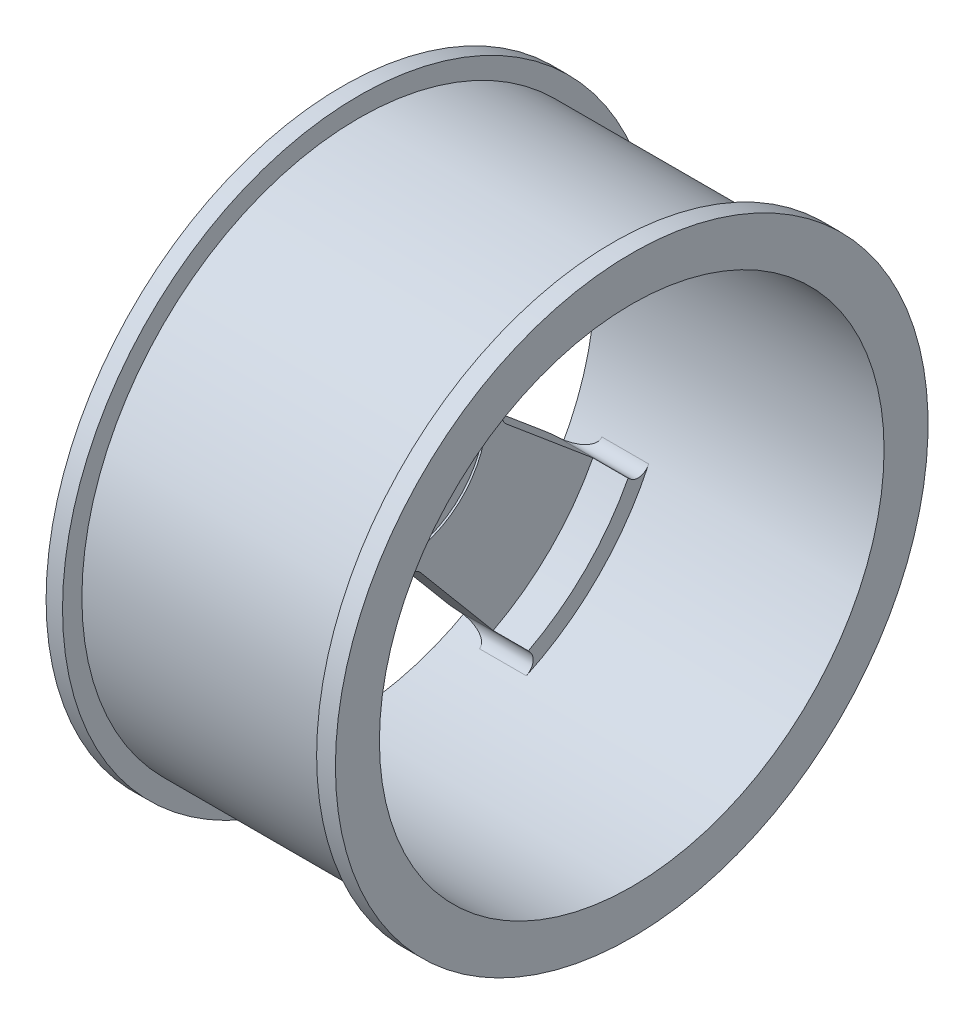
SolidWorks part; units mm, degrees
material "6061-T6 (SS)"
ref_plane "Front Plane" through (0, 0, 0) normal (0, 0, 1) x (1, 0, 0)
ref_plane "Top Plane" through (0, 0, 0) normal (0, 1, 0) x (1, 0, 0)
ref_plane "Right Plane" through (0, 0, 0) normal (1, 0, 0) x (0, 0, -1)
sketch "Sketch1" plane through (0, 0, 0) normal (0, 0, 1) x (1, 0, 0)
  line L0 (0, 0) -> (59.4628, 0) construction
  line L1 (0, 202) -> (0, 172)
  line L2 (0, 172) -> (28.8, 172)
  line L3 (28.8, 172) -> (28.8, 160)
  line L4 (28.8, 160) -> (52.8, 160)
  line L5 (52.8, 160) -> (52.8, 172)
  line L6 (52.8, 172) -> (197.2, 172)
  line L7 (197.2, 172) -> (197.2, 202)
  line L8 (197.2, 202) -> (184.4, 202)
  line L9 (184.4, 202) -> (184.4, 188.8)
  line L10 (184.4, 188.8) -> (11.2, 188.8)
  line L11 (11.2, 188.8) -> (11.2, 202)
  line L12 (11.2, 202) -> (0, 202)
  dimension "D1" = 202
  dimension "D2" = 188.8
  dimension "D3" = 172
  dimension "D4" = 160
  dimension "D5" = 28.8
  dimension "D6" = 24
  dimension "D7" = 11.2
  dimension "D8" = 12.8
  dimension "D9" = 197.2
revolve "Revolve1" add sketch "Sketch1" angle 360 about L0
sketch "Sketch2" plane through (0, 0, 0) normal (0, 0, 1) x (1, 0, 0)
  line L0 (-3.1546, 0) -> (32.0631, 0) construction
  line L1 (12, 0) -> (12, 74)
  line L2 (12, 74) -> (70.8897, 40)
  line L3 (70.8897, 40) -> (217.6, 40)
  line L4 (217.6, 40) -> (217.6, 0)
  line L5 (217.6, 0) -> (12, 0)
  line L6 (0, 172) -> (0, -172) construction
  dimension "D1" = 74
  dimension "D2" = 12
  dimension "D3" = 40
  dimension "D4" = 60
  dimension "D5" = 205.6
revolve "Revolve2" add sketch "Sketch2" angle 360 about L0
sketch "Sketch4" plane through (0, 0, 0) normal (0, 0, 1) x (1, 0, 0)
  line L0 (28.8, 172) -> (20.7846, 172)
  line L1 (28.8, 172) -> (28.8, -172) construction
  line L2 (20.7846, 172) -> (0, 160)
  line L3 (0, 172) -> (0, -172) construction
  line L4 (0, 160) -> (0, 0)
  line L5 (0, 0) -> (12, 0)
  line L6 (12, 74) -> (12, -74) construction
  line L7 (12, 0) -> (12, 10.8005)
  line L8 (12, 10.8005) -> (28.8, 20.5)
  line L9 (28.8, 160) -> (28.8, -160) construction
  line L10 (28.8, 20.5) -> (28.8, 172)
  dimension "D3" = 172
  dimension "D1" = 12
  dimension "D2" = 160
  dimension "D4" = 20.5
  dimension "D5" = 120
  dimension "D6" = 151.5
  dimension "D7" = 8.0154
revolve "Revolve3" add sketch "Sketch4" angle 360 about L5
fillet "Fillet1" radius 8 1 edges at (0, 0, 160)
sketch "Sketch5" plane through (0, 0, 0) normal (-1, 0, 0) x (0, 0, 1)
  line L0 (0, 0) -> (0, 202) construction
  line L1 (22, 80) -> (-22, 80)
  line L2 (-22, 80) -> (-81.8212, 151.2921)
  line L3 (22, 80) -> (81.8212, 151.2921)
  line L4 (80, 22) -> (151.2921, 81.8212)
  line L5 (80, -22) -> (80, 22)
  line L6 (80, -22) -> (151.2921, -81.8212)
  line L7 (22, -80) -> (81.8212, -151.2921)
  line L8 (-22, -80) -> (22, -80)
  line L9 (-22, -80) -> (-81.8212, -151.2921)
  line L10 (-80, -22) -> (-151.2921, -81.8212)
  line L11 (-80, 22) -> (-80, -22)
  line L12 (-80, 22) -> (-151.2921, 81.8212)
  circle A0 centre (0, 0) radius 202 construction
  circle A3 centre (0, 0) radius 172 construction
  arc A4 (81.8212, 151.2921) -> (-81.8212, 151.2921) centre (0, 0) ccw
  arc A5 (151.2921, -81.8212) -> (151.2921, 81.8212) centre (0, 0) ccw
  arc A6 (-81.8212, -151.2921) -> (81.8212, -151.2921) centre (0, 0) ccw
  arc A7 (-151.2921, 81.8212) -> (-151.2921, -81.8212) centre (0, 0) ccw
  point P13 (0, 80)
  point P28 (0, 0)
  dimension "D1" = 44
  dimension "D2" = 80
  dimension "D3" = 130
  dimension "D4" = 130
  dimension "D5" = 4
extrude "Cut-Extrude3" cut sketch "Sketch5" against normal through all
fillet "Fillet4" radius 8 2 edges at (14.4, 80, 22) (14.4, 80, -22)
fillet "Fillet6" radius 8 2 edges at (14.4, -22, 80) (14.4, 22, 80)
fillet "Fillet7" radius 8 8 edges at (36.7923, -151.2921, -81.8212) (36.7923, -81.8212, -151.2921) (36.7923, -151.2921, 81.8212) (36.7923, 81.8212, -151.2921) (14.4, -80, -22) (14.4, -80, 22) (14.4, -22, -80) (14.4, 22, -80)
sketch "Sketch7" plane through (0, 0, 0) normal (0, 0, 1) x (1, 0, 0)
  line L0 (0, 0) -> (17.1078, 0) construction
  line L1 (0, 0) -> (0, 68)
  line L2 (0, 24.3979) -> (0, 70.8916) construction
  line L3 (0, 68) -> (24.8, 53.6817)
  line L4 (24.8, 53.6817) -> (24.8, 0)
  line L5 (24.8, 0) -> (0, 0)
  dimension "D1" = 24.8
  dimension "D2" = 68
  dimension "D3" = 60
revolve "Cut-Revolve3" cut sketch "Sketch7" angle 360 about L0
sketch "Sketch8" plane through (24.8, 0, 0) normal (-1, 0, 0) x (0, 0, 1)
  circle A0 centre (0, 0) radius 36
  circle A1 centre (0, 44.45) radius 3.937
  circle A2 centre (44.45, 0) radius 3.937
  circle A3 centre (0, 0) radius 36
  circle A4 centre (0, -44.45) radius 3.937
  circle A5 centre (0, 0) radius 36
  circle A6 centre (-44.45, 0) radius 3.937
  circle A7 centre (0, 0) radius 36
  point P17 (0, 0)
  dimension "D1" = 72
  dimension "D2" = 7.874
  dimension "D3" = 44.45
  dimension "D4" = 4
extrude "Boss-Extrude1" add sketch "Sketch8" along normal blind 1 contours A0 region at (24.8, 0, 0)
extrude "Cut-Extrude6" cut sketch "Sketch8<6>" against normal through all contours A1 | A2 | A4 | A6 region at (24.8, 44.45, 0) region at (24.8, 0, 44.45) region at (24.8, -44.45, 0)
sketch "Sketch8<6>" plane through (24.8, 0, 0) normal (-1, 0, 0) x (0, 0, 1) same geometry as "Sketch8"
sketch "Sketch9" plane through (217.6, 0, 0) normal (1, 0, 0) x (0, 0, -1)
  circle A0 centre (0, 0) radius 57.15
  dimension "D1" = 114.3
extrude "Cut-Extrude7" cut sketch "Sketch9" against normal blind 177.8
equation "\"scale\"= 8"
equation "\"D7@Sketch1\"=1.40mm * \"scale\""
equation "\"D9@Sketch1\"=24.65mm * \"scale\""
equation "\"D8@Sketch1\"=1.60mm * \"scale\""
equation "\"D1@Sketch1\"=25.25mm * \"scale\""
equation "\"D2@Sketch1\"=23.60mm * \"scale\""
equation "\"D3@Sketch1\"=21.50mm * \"scale\""
equation "\"D4@Sketch1\"=20.00mm * \"scale\""
equation "\"D5@Sketch1\"=3.60mm * \"scale\""
equation "\"D6@Sketch1\"=3.00mm * \"scale\""
equation "\"D1@Sketch2\"=9.25mm * \"scale\""
equation "\"D3@Sketch2\"=5.00mm * \"scale\""
equation "\"D2@Sketch2\"=1.50mm * \"scale\""
equation "\"D5@Sketch2\"=25.70mm * \"scale\""
equation "\"D1@Fillet1\"= 1mm * \"scale\""
equation "\"D1@Sketch5\"=5.50mm * \"scale\""
equation "\"D2@Sketch5\"=10.00mm * \"scale\""
equation "\"D1@Fillet7\"=1.00mm * \"scale\""
equation "\"D2@Sketch7\"=8.50mm * \"scale\""
equation "\"D1@Sketch7\"=3.10mm * \"scale\""
equation "\"D3@Sketch8\"=1.75"
equation "\"D1@Sketch8\"=9.00mm * \"scale\""
equation "\"D3@Sketch4\"=0.84645669in * \"scale\""
equation "\"D2@Sketch4\"=0.78740157in * \"scale\""
equation "\"D1@Fillet4\"=1.00mm * \"scale\""
equation "\"D1@Fillet6\"=1.00mm * \"scale\""
